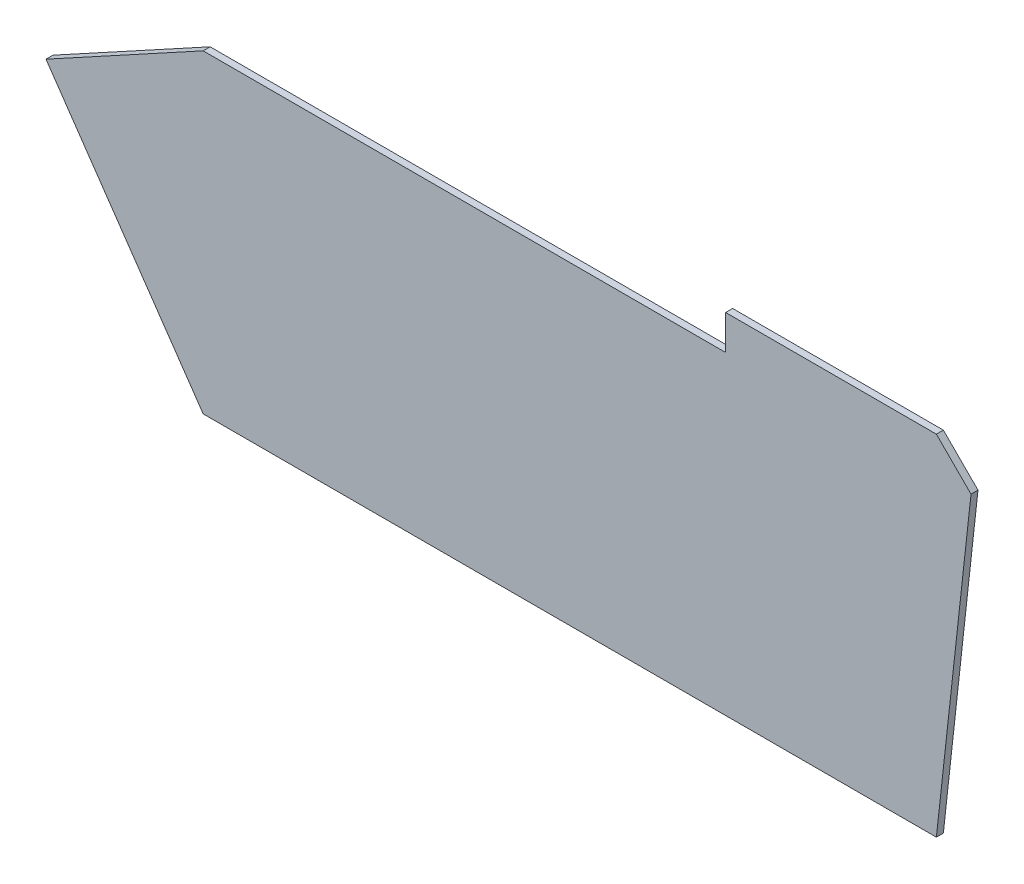
SolidWorks part; units mm, degrees
ref_plane "Front Plane" through (0, 0, 0) normal (0, 0, 1) x (1, 0, 0)
ref_plane "Top Plane" through (0, 0, 0) normal (0, 1, 0) x (1, 0, 0)
ref_plane "Right Plane" through (0, 0, 0) normal (1, 0, 0) x (0, 0, -1)
sketch "Sketch1" plane through (0, 0, 0) normal (0, 0, 1) x (1, 0, 0)
  line L0 (192.0393, 88.9838) -> (201.963, 79.0601)
  line L5 (201.963, 79.0601) -> (192.0393, -11.0162)
  line L6 (192.0393, -11.0162) -> (-18.008, -11.0162)
  line L8 (-18.008, 79.0601) -> (131.6712, 79.0601)
  line L9 (131.6712, 79.0601) -> (131.6712, 88.9838)
  line L10 (131.6712, 88.9838) -> (192.0393, 88.9838)
  line L11 (-18.008, 79.0601) -> (-63.037, 54.4726)
  line L12 (-63.037, 54.4726) -> (-18.008, -11.0162)
  point P0 (0, 0)
extrude "Boss-Extrude1" add sketch "Sketch1" along normal blind 2
